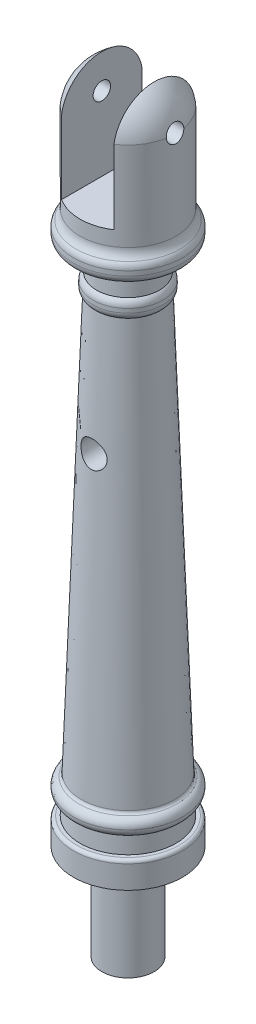
SolidWorks part; units mm, degrees
ref_plane "Front Plane" through (0, 0, 0) normal (0, 0, 1) x (1, 0, 0)
ref_plane "Top Plane" through (0, 0, 0) normal (0, 1, 0) x (1, 0, 0)
ref_plane "Right Plane" through (0, 0, 0) normal (1, 0, 0) x (0, 0, -1)
sketch "Sketch1" plane through (0, 0, 0) normal (0, 0, 1) x (1, 0, 0)
  line L0 (0, 0) -> (0, 114)
  line L1 (0, 114) -> (7, 114)
  line L2 (7, 114) -> (11, 0)
  line L3 (11, 0) -> (0, 0)
  dimension "D1" = 114
  dimension "D2" = 7
  dimension "D3" = 11
revolve "Revolve1" add sketch "Sketch1" angle 360 about L0
sketch "Sketch2" plane through (0, 0, 0) normal (0, -1, 0) x (1, 0, 0)
  circle A0 centre (0, 0) radius 12.5
  dimension "D1" = 25
extrude "Boss-Extrude1" add sketch "Sketch2" along normal blind 6
sketch "Sketch3" plane through (0, -6, 0) normal (0, -1, 0) x (1, 0, 0)
  circle A1 centre (0, 0) radius 12.5
  circle A2 centre (0, 0) radius 12.5
  dimension "D1" = 0
extrude "Boss-Extrude2" add sketch "Sketch3" along normal mid plane 4 from offset 12 offset against normal yes
fillet "Fillet1" radius 2 2 edges at (0, 8, -12.5) (0, 4, -12.5)
fillet "Fillet2" radius 0.75 1 edges at (0, 0, -12.5)
sketch "Sketch4" plane through (0, -6, 0) normal (0, -1, 0) x (1, 0, 0)
  circle A0 centre (0, 0) radius 6
  dimension "D1" = 12
extrude "Boss-Extrude3" add sketch "Sketch4" along normal blind 22
sketch "Sketch5" plane through (0, -28, 0) normal (0, -1, 0) x (1, 0, 0)
  line L0 (-5, 3.3166) -> (-5, -3.3166)
  circle A1 centre (0, 0) radius 6
  arc A2 (-5, 3.3166) -> (-5, -3.3166) centre (0, 0) ccw
  dimension "D2" = 5
  dimension "D1" = 0
extrude "Cut-Extrude1" cut sketch "Sketch5" against normal blind 15
sketch "Sketch6" plane through (0, 114, 0) normal (0, 1, 0) x (1, 0, 0)
  circle A0 centre (0, 0) radius 8
  dimension "D1" = 16
extrude "Boss-Extrude4" add sketch "Sketch6" along normal mid plane 4 from offset 8 offset against normal yes
fillet "Fillet3" radius 2 2 edges at (0, 104, 8) (0, 108, 8)
sketch "Sketch7" plane through (0, 114, 0) normal (0, 1, 0) x (1, 0, 0)
  circle A0 centre (0, 0) radius 12.5
  dimension "D1" = 25
extrude "Boss-Extrude5" add sketch "Sketch7" along normal blind 5
sketch "Sketch8" plane through (0, 119, 0) normal (0, 1, 0) x (1, 0, 0)
  circle A0 centre (0, 0) radius 11
  dimension "D1" = 22
extrude "Boss-Extrude6" add sketch "Sketch8" along normal blind 22
fillet "Fillet4" radius 2 2 edges at (0, 114, 12.5) (0, 119, 12.5)
fillet "Fillet5" radius 3 1 edges at (0, 119, 11)
fillet "Fillet6" radius 0.75 1 edges at (0, 8, -10.7193)
sketch "Sketch9" plane through (0, 0, 0) normal (0, 0, 1) x (1, 0, 0)
  line L0 (11, 141) -> (0, 141)
  line L1 (11, 141) -> (-11, 141) construction
  line L2 (0, 141) -> (0, 150.5)
  arc A0 (0, 150.5) -> (11, 141) centre (0.1027, 139.5005) cw
  dimension "D2" = 11
  dimension "D1" = 9.5
revolve "Revolve2" add sketch "Sketch9" angle 360 about L2
sketch "Sketch10" plane through (0, 0, 0) normal (0, 0, 1) x (1, 0, 0)
  line L0 (0, 120.6342) -> (0, 155.9667) construction
  line L1 (11, 120.6342) -> (-11, 120.6342) construction
  line L2 (11, 141) -> (-11, 141) construction
  line L3 (-6, 152) -> (6, 152)
  line L4 (-6, 152) -> (-6, 124)
  line L5 (-6, 124) -> (6, 124)
  line L6 (6, 152) -> (6, 124)
  dimension "D1" = 17
  dimension "D2" = 12
  dimension "D3" = 28
extrude "Cut-Extrude2" cut sketch "Sketch10" against normal through all both and the other way through all
sketch "Sketch11" plane through (0, 0, 0) normal (0, 0, 1) x (1, 0, 0)
  line L0 (-12.5, -6) -> (12.5, -6) construction
  circle A0 centre (0, 76) radius 3
  dimension "D2" = 6
  dimension "D1" = 82
extrude "Cut-Extrude3" cut sketch "Sketch11" against normal through all both and the other way through all
sketch "Sketch12" plane through (0, 0, 0) normal (1, 0, 0) x (0, 0, -1)
  line L0 (-9.2195, 141) -> (9.2195, 141) construction
  circle A0 centre (0, 141) radius 2
  dimension "D1" = 4
extrude "Cut-Extrude4" cut sketch "Sketch12" against normal through all both and the other way through all
